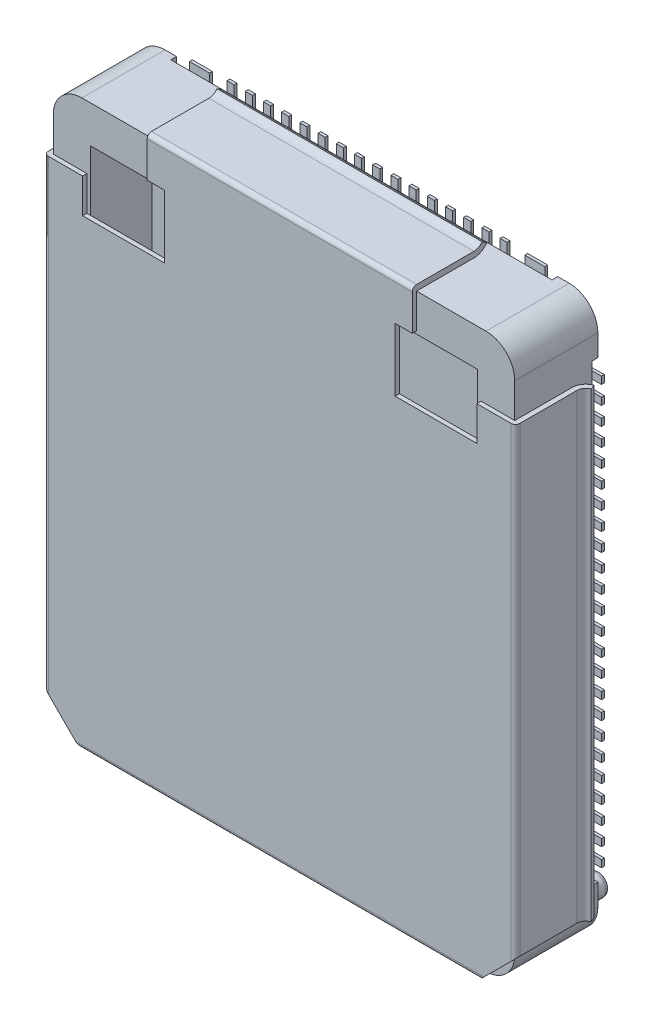
SolidWorks part; units mm, degrees
ref_plane "Plan de face" through (0, 0, 0) normal (0, 0, 1) x (1, 0, 0)
ref_plane "Plan de dessus" through (0, 0, 0) normal (0, 1, 0) x (1, 0, 0)
ref_plane "Plan de droite" through (0, 0, 0) normal (1, 0, 0) x (0, 0, -1)
sketch "Esquisse1" plane through (0, 0, 0) normal (0, 0, 1) x (1, 0, 0)
  line L1 (-14.1, 19.35) -> (14.1, 19.35)
  line L2 (-16.1, 17.35) -> (-16.1, -17.35)
  line L3 (-14.1, -19.35) -> (14.1, -19.35)
  line L4 (16.1, 17.35) -> (16.1, -17.35)
  line L5 (-16.1, 19.35) -> (16.1, -19.35) construction
  line L6 (-16.1, -19.35) -> (16.1, 19.35) construction
  arc A0 (16.1, -17.35) -> (14.1, -19.35) centre (14.1, -17.35) cw
  arc A1 (-14.1, -19.35) -> (-16.1, -17.35) centre (-14.1, -17.35) cw
  arc A2 (-16.1, 17.35) -> (-14.1, 19.35) centre (-14.1, 17.35) cw
  arc A3 (14.1, 19.35) -> (16.1, 17.35) centre (14.1, 17.35) cw
  point P0 (0, 0)
  dimension "D3" = 2
  dimension "D1" = 32.2
  dimension "D2" = 38.7
extrude "base" add sketch "Esquisse1" along normal blind 5.8 from offset 0.2
sketch "Esquisse2" plane through (0, 0, 6) normal (0, 0, 1) x (1, 0, 0)
  line L0 (14.1, 19.35) -> (-14.1, 19.35) construction
  line L1 (-13.5, -16.75) -> (13.5, -16.75)
  line L2 (-13.5, -16.75) -> (-13.5, 16.75)
  line L3 (-13.5, 16.75) -> (13.5, 16.75)
  line L4 (13.5, -16.75) -> (13.5, 16.75)
  line L5 (-13.5, -16.75) -> (13.5, 16.75) construction
  line L6 (-13.5, 16.75) -> (13.5, -16.75) construction
  line L7 (16.1, -17.35) -> (16.1, 17.35) construction
  point P0 (0, 0)
  dimension "D1" = 2.6
  dimension "D2" = 2.6
extrude "logement module" cut sketch "Esquisse2" against normal blind 4.3
sketch "Esquisse4" plane through (0, 0, 0) normal (0, 1, 0) x (1, 0, 0)
  line L0 (14.1, -6) -> (-14.1, -6) construction
  line L1 (-13.3, 0.6) -> (13.3, 0.6)
  line L2 (-13.3, 0.6) -> (-13.3, -0.6)
  line L3 (-13.3, -0.6) -> (13.3, -0.6)
  line L4 (13.3, 0.6) -> (13.3, -0.6)
  line L5 (-13.3, 0.6) -> (13.3, -0.6) construction
  line L6 (-13.3, -0.6) -> (13.3, 0.6) construction
  point P0 (0, 0)
  dimension "D1" = 26.6
  dimension "D2" = 5.4
extrude "passage pins x" cut sketch "Esquisse4" against normal through all both and the other way through all
sketch "Esquisse5" plane through (0, 0, 0) normal (1, 0, 0) x (0, 0, -1)
  line L0 (-6, -17.35) -> (-6, 17.35) construction
  line L1 (-0.6, 15.85) -> (0.6, 15.85)
  line L2 (-0.6, 15.85) -> (-0.6, -15.85)
  line L3 (-0.6, -15.85) -> (0.6, -15.85)
  line L4 (0.6, 15.85) -> (0.6, -15.85)
  line L5 (-0.6, 15.85) -> (0.6, -15.85) construction
  line L6 (-0.6, -15.85) -> (0.6, 15.85) construction
  point P0 (0, 0)
  dimension "D1" = 5.4
  dimension "D2" = 31.7
extrude "passage pins y" cut sketch "Esquisse5" against normal through all both and the other way through all
sketch "Esquisse3" plane through (0, 0, 0) normal (0, 1, 0) x (1, 0, 0)
  line L0 (-14.65, -1.2066) -> (-14.65, -0.3)
  line L2 (-14.95, 0) -> (-16.35, 0)
  line L3 (-14.85, -1.2066) -> (-14.85, -0.3)
  line L4 (-14.95, -0.2) -> (-16.35, -0.2)
  line L5 (-16.35, 0) -> (-16.35, -0.2)
  line L6 (0, 1.3536) -> (0, -1.0635) construction
  line L7 (-14.65, -0.5322) -> (-14.65, -0.3) construction
  line L8 (-14.85, -0.5322) -> (-14.85, -0.3) construction
  line L9 (-14.65, -1.2066) -> (-14.85, -1.2066)
  arc A0 (-14.65, -0.3) -> (-14.95, 0) centre (-14.95, -0.3) ccw
  arc A1 (-14.85, -0.3) -> (-14.95, -0.2) centre (-14.95, -0.3) ccw
  dimension "D3" = 0.3
  dimension "D2" = 32.7
  dimension "D4" = 29.3
  dimension "D1" = 0.2
extrude "pin1" add sketch "Esquisse3" along normal mid plane 0.5 from offset 14.605
sketch "Esquisse6" plane through (0, 0, 0) normal (1, 0, 0) x (0, 0, -1)
  line L0 (-1.1472, 17.95) -> (-0.3078, 17.95)
  line L1 (0, 18.2578) -> (0, 19.65)
  line L2 (-1.1472, 18.15) -> (-0.3078, 18.15)
  line L3 (-0.2, 18.2578) -> (-0.2, 19.65)
  line L4 (0, 19.65) -> (-0.2, 19.65)
  line L5 (-1.1472, 18.15) -> (-1.1472, 17.95)
  line L6 (0, 14.855) -> (0, 14.355) construction
  line L7 (0, 0) -> (-3.7905, 0) construction
  arc A0 (-0.3078, 17.95) -> (0, 18.2578) centre (-0.3078, 18.2578) ccw
  arc A1 (-0.3078, 18.15) -> (-0.2, 18.2578) centre (-0.3078, 18.2578) ccw
  dimension "D2" = 1.7
  dimension "D3" = 35.9
  dimension "D1" = 0.2
extrude "pin 80" add sketch "Esquisse6" along normal mid plane 0.5 from offset 9.525 offset against normal yes
pattern_linear "Répétition linéaire pins y" count 24 spacing 1.27 along (0, -1, 0) of "pin1"
mirror "Symétrie pins y" about plane through (0, 0, 0) normal (1, 0, 0) of "Répétition linéaire pins y"
pattern_linear "Répétition linéaire pins x" count 16 spacing 1.27 along (1, 0, 0) of "pin 80"
mirror "Symétrie pins x" about plane through (0, 0, 0) normal (0, 1, 0) of "Répétition linéaire pins x"
sketch "Esquisse7" plane through (0, 0, 0) normal (1, 0, 0) x (0, 0, -1)
  line L0 (0, 19.5) -> (0, 18.2578)
  line L1 (-0.2578, 18) -> (-6, 18)
  line L2 (-6, 19.35) -> (-6, 17.35) construction
  line L3 (-0.2, 19.5) -> (-0.2, 18.2578)
  line L4 (-0.2578, 18.2) -> (-6, 18.2)
  line L5 (0, 19.5) -> (-0.2, 19.5)
  line L6 (-6, 18.2) -> (-6, 18)
  line L7 (0, 0) -> (-3.1967, 0) construction
  arc A0 (0, 18.2578) -> (-0.2578, 18) centre (-0.2578, 18.2578) cw
  arc A1 (-0.2, 18.2578) -> (-0.2578, 18.2) centre (-0.2578, 18.2578) cw
  dimension "D2" = 39
  dimension "D3" = 36
  dimension "D1" = 0.2
extrude "pin meca" add sketch "Esquisse7" along normal mid plane 1.4 from offset 11.7 offset against normal yes
mirror "Symétrie pins meca x" about plane through (0, 0, 0) normal (1, 0, 0) of "pin meca"
mirror "Symétrie pins meca y" about plane through (0, 0, 0) normal (0, 1, 0) of "Symétrie pins meca x"
sketch "Esquisse8" plane through (0, 0, 0.2) normal (0, 0, -1) x (-1, 0, 0)
  line L0 (0, 0) -> (0, 20.506) construction
  circle A0 centre (-15, -17) radius 0.75
  point P5 (-14.95, -16.8463)
  dimension "D1" = 1.5
  dimension "D2" = 30
  dimension "D3" = 17
extrude "detrompeur" add sketch "Esquisse8" along normal blind 1.2
fillet "Congé detrompeur" radius 0.3 1 edges at (14.25, -17, -1)
mirror "Symétrie5" about plane through (0, 0, 0) normal (1, 0, 0) of "Congé detrompeur", "detrompeur"
sketch "Esquisse9" plane through (0, 0, 6) normal (0, 0, 1) x (1, 0, 0)
  line L0 (-9.25, 19.75) -> (-9.25, 16.95)
  line L1 (13.95, -19.75) -> (-13.95, -19.75)
  line L2 (-9.25, 16.95) -> (-8.05, 16.95)
  line L3 (-8.05, 16.95) -> (-8.05, 12.55)
  line L4 (-8.05, 12.55) -> (-13.75, 12.55)
  line L5 (-13.75, 12.55) -> (-13.75, 14.95)
  line L6 (-13.75, 14.95) -> (-16.45, 14.95)
  line L7 (-16.45, 14.95) -> (-16.45, -17.25)
  line L9 (-16.45, -17.25) -> (-13.95, -19.75)
  line L10 (-14.1, -19.35) -> (14.1, -19.35) construction
  line L12 (0, 21.5205) -> (0, -23.3196) construction
  line L13 (-9.25, 19.75) -> (9.25, 19.75)
  line L14 (16.45, -17.25) -> (13.95, -19.75)
  line L15 (16.45, 14.95) -> (16.45, -17.25)
  line L16 (13.75, 14.95) -> (16.45, 14.95)
  line L17 (13.75, 12.55) -> (13.75, 14.95)
  line L18 (8.05, 12.55) -> (13.75, 12.55)
  line L19 (8.05, 16.95) -> (8.05, 12.55)
  line L20 (9.25, 16.95) -> (8.05, 16.95)
  line L21 (9.25, 19.75) -> (9.25, 16.95)
  line L24 (-10.5913, 0) -> (7.0351, 0) construction
  point P21 (0, -19.35)
  point P30 (0, 19.75)
  dimension "D1" = 27.9
  dimension "D2" = 135
  dimension "D3" = 32.2
  dimension "D4" = 18.5
  dimension "D5" = 5.7
  dimension "D6" = 32.9
  dimension "D7" = 39.5
  dimension "D8" = 2.7
  dimension "D9" = 2.8
  dimension "D10" = 4.4
extrude "capot top" add sketch "Esquisse9" along normal blind 0.3
sketch "Esquisse10" plane through (0, 0, 0) normal (0, 1, 0) x (1, 0, 0)
  line L0 (16.1, -6) -> (16.1, -2)
  line L1 (16.1, -6) -> (16.1, -0.2) construction
  line L2 (16.45, -6) -> (16.45, -2)
  line L3 (16.45, -6) -> (16.45, -2) construction
  line L4 (16.7304, -1.1) -> (16.85, -1.4289)
  line L5 (16.45, -6) -> (16.1, -6)
  line L6 (0, 0) -> (0, -4.5104) construction
  line L7 (-16.45, -6) -> (-16.1, -6)
  line L8 (-16.1, -6) -> (-16.1, -2)
  line L9 (-16.7304, -1.1) -> (-16.85, -1.4289)
  line L10 (-16.45, -6) -> (-16.45, -2)
  line L11 (16.45, -6.3) -> (13.75, -6.3) construction
  arc A0 (16.1, -2) -> (16.7304, -1.1) centre (17.0577, -2) cw
  arc A1 (16.45, -2) -> (16.85, -1.4289) centre (17.0577, -2) cw
  arc A2 (-16.1, -2) -> (-16.7304, -1.1) centre (-17.0577, -2) ccw
  arc A3 (-16.45, -2) -> (-16.85, -1.4289) centre (-17.0577, -2) ccw
  dimension "D1" = 33.7
  dimension "D2" = 4
  dimension "D3" = 5.2
  dimension "D4" = 0.75
extrude "capot cote x" add sketch "Esquisse10" along direction (0, 1, 0) on the side of the normal up to vertex (14.95 mm away) and the other way up to vertex (17.25 mm away) up to point (16.45, 14.95, 6) other way up to point (16.45, -17.25, 6)
sketch "Esquisse11" plane through (0, 0, 0) normal (1, 0, 0) x (0, 0, -1)
  line L0 (-6, 19.35) -> (-2, 19.35)
  line L1 (-6, 19.35) -> (-0.2, 19.35) construction
  line L2 (-1.1, 19.8217) -> (-1.4289, 20.0493)
  line L3 (-6, 19.75) -> (-2, 19.75)
  line L4 (-2, 14.95) -> (-2, -17.25) construction
  line L5 (-6, 19.75) -> (-2, 19.75) construction
  line L6 (-1.1, 19.8217) -> (-1.0303, 19.9225) construction
  line L7 (-1.4289, 20.0493) -> (-1.3592, 20.1501) construction
  line L8 (-1.1, 14.95) -> (-1.1, -17.25) construction
  line L9 (-1.4289, 14.95) -> (-1.4289, -17.25) construction
  line L10 (-6, 19.75) -> (-6, 19.35)
  arc A0 (-2, 19.35) -> (-1.1, 19.8217) centre (-2, 20.4445) ccw
  arc A1 (-2, 19.75) -> (-1.4289, 20.0493) centre (-2, 20.4445) ccw
extrude "Boss.-Extru.9" add sketch "Esquisse11" along normal up to vertex (9.25 mm away) and the other way up to vertex (9.25 mm away) up to point (9.25, 19.75, 6) other way up to point (-9.25, 19.75, 6)
sketch "Esquisse12" plane through (0, 0, 0) normal (1, 0, 0) x (0, 0, -1)
  line L0 (-6, -19.35) -> (-2, -19.35)
  line L1 (-6, -19.35) -> (-0.2, -19.35) construction
  line L2 (-6, -19.75) -> (-2, -19.75)
  line L3 (-5.8658, -19.75) -> (-2, -19.75) construction
  line L4 (-5.8658, -19.35) -> (-2, -19.35) construction
  line L5 (-6, -19.75) -> (-6, -19.332) construction
  line L6 (-1.1, -19.8217) -> (-1.4289, -20.0493)
  line L7 (-2, 14.95) -> (-2, -17.25) construction
  line L8 (-1.4289, 14.95) -> (-1.4289, -17.25) construction
  line L9 (-1.1, 14.95) -> (-1.1, -17.25) construction
  line L10 (-6, -19.35) -> (-6, -19.75)
  arc A0 (-2, -19.35) -> (-1.1, -19.8217) centre (-2, -20.4445) cw
  arc A1 (-2, -19.75) -> (-1.4289, -20.0493) centre (-2, -20.4445) cw
extrude "Boss.-Extru.10" add sketch "Esquisse12" along normal up to vertex (13.95 mm away) and the other way up to vertex (13.95 mm away) up to point (13.95, -19.75, 6) other way up to point (-13.95, -19.75, 6)
fillet "Congé2" radius 0.3 4 edges at (0, 19.75, 6.3) (-16.45, -1.15, 6.3) (0, -19.75, 6.3) (16.45, -1.15, 6.3)
